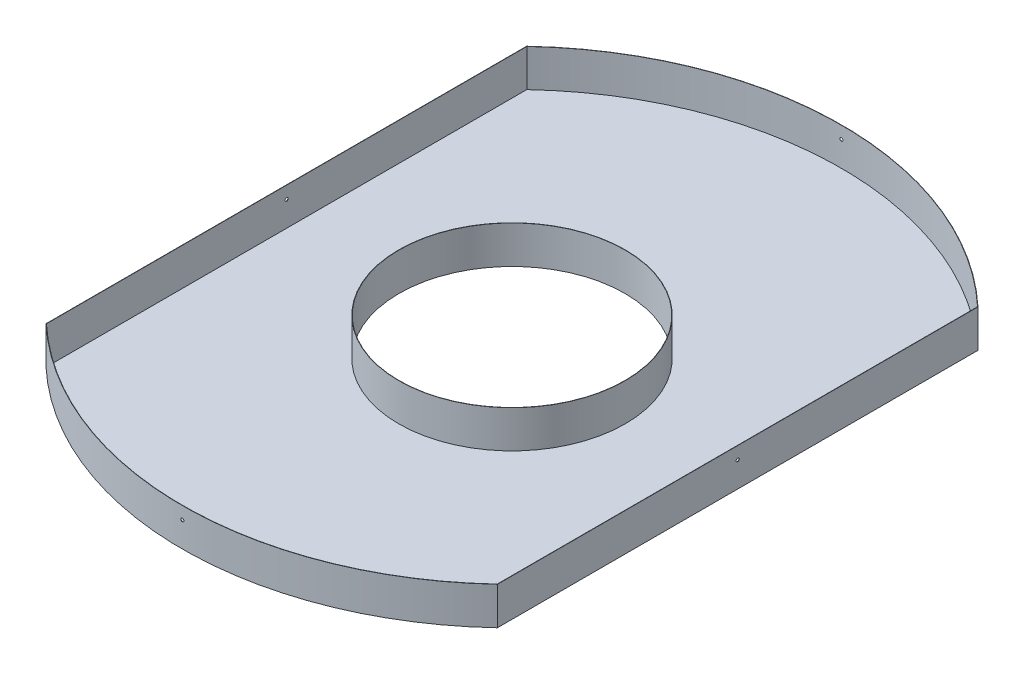
SolidWorks part; units mm, degrees
material "1345 Alloy"
ref_plane "Front Plane" through (0, 0, 0) normal (0, 0, 1) x (1, 0, 0)
ref_plane "Top Plane" through (0, 0, 0) normal (0, 1, 0) x (1, 0, 0)
ref_plane "Right Plane" through (0, 0, 0) normal (1, 0, 0) x (0, 0, -1)
sketch "Sketch1" plane through (0, 0, 0) normal (0, 1, 0) x (1, 0, 0)
  circle A0 centre (0, 0) radius 1750
extrude "Boss-Extrude1" add sketch "Sketch1" along normal blind 500
sketch "Sketch2" plane through (0, 500, 0) normal (0, 1, 0) x (1, 0, 0)
  circle A0 centre (0, 0) radius 900
extrude "Cut-Extrude2" cut sketch "Sketch2" against normal blind 300
sketch "Sketch10" plane through (0, 500, 0) normal (0, 1, 0) x (1, 0, 0)
  line L1 (-2200.588, -2811.5432) -> (2200.588, -2811.5432)
  line L2 (-2200.588, -2811.5432) -> (-2200.588, 2811.5432)
  line L3 (-2200.588, 2811.5432) -> (2200.588, 2811.5432)
  line L4 (2200.588, -2811.5432) -> (2200.588, 2811.5432)
  line L5 (-2200.588, -2811.5432) -> (2200.588, 2811.5432) construction
  line L6 (-2200.588, 2811.5432) -> (2200.588, -2811.5432) construction
  line L7 (-1198.0599, -2169.9586) -> (1198.0599, -2169.9586)
  line L8 (-1198.0599, -2169.9586) -> (-1198.0599, 2169.9586)
  line L9 (-1198.0599, 2169.9586) -> (1198.0599, 2169.9586)
  line L10 (1198.0599, -2169.9586) -> (1198.0599, 2169.9586)
  line L11 (-1198.0599, -2169.9586) -> (1198.0599, 2169.9586) construction
  line L12 (-1198.0599, 2169.9586) -> (1198.0599, -2169.9586) construction
  point P0 (0, 0)
  point P6 (0, 0)
extrude "Cut-Extrude10" cut sketch "Sketch10" against normal through all both and the other way through all
sketch "Sketch3" plane through (0, 0, 0) normal (0, -1, 0) x (1, 0, 0)
  circle A0 centre (0, 0) radius 600
extrude "Cut-Extrude3" cut sketch "Sketch3" against normal blind 300
shell "Shell1" thickness 1.5 removed face at (0, 500, 900)
sketch "Sketch11" plane through (0, 200, 0) normal (0, 1, 0) x (1, 0, 0)
  line L1 (-1546.6788, 2430.4952) -> (1546.6788, 2430.4952)
  line L2 (-1546.6788, 2430.4952) -> (-1546.6788, -2430.4952)
  line L3 (-1546.6788, -2430.4952) -> (1546.6788, -2430.4952)
  line L4 (1546.6788, 2430.4952) -> (1546.6788, -2430.4952)
  line L5 (-1546.6788, 2430.4952) -> (1546.6788, -2430.4952) construction
  line L6 (-1546.6788, -2430.4952) -> (1546.6788, 2430.4952) construction
  point P0 (0, 0)
extrude "Cut-Extrude11" cut sketch "Sketch11" along normal through all
ref_plane "Plane1" through (0, 0, 2000) normal (0, 0, 1) x (1, 0, 0)
sketch "Sketch7" plane through (0, 0, 2000) normal (0, 0, 1) x (1, 0, 0)
  circle A0 centre (0, 133.8976) radius 8.382
extrude "Cut-Extrude6" cut sketch "Sketch7" against normal blind 900
pattern_circular "CirPattern1" count 4 over 360 about axis through (0, 500, 0) along (0, -1, 0) of "Cut-Extrude6" reverse direction yes
ref_plane "Plane2" through (-1237.4369, 0, 1237.4369) normal (-0.7071, 0, 0.7071) x (0, -1, 0)
sketch "Sketch12" plane through (-1198.0599, 0, 0) normal (-1, 0, 0) x (0, 0, 1)
  line L0 (-828.0253, 88.1097) -> (-805.4725, 65.5569)
  line L1 (-805.4725, 65.5569) -> (-773.578, 65.5569)
  line L2 (-773.578, 65.5569) -> (-751.0253, 88.1097)
  line L3 (-751.0253, 88.1097) -> (-751.0253, 120.0042)
  line L4 (-751.0253, 120.0042) -> (-773.578, 142.5569)
  line L5 (-773.578, 142.5569) -> (-805.4725, 142.5569)
  line L6 (-805.4725, 142.5569) -> (-828.0253, 120.0042)
  line L7 (-828.0253, 120.0042) -> (-828.0253, 88.1097)
  circle A0 centre (-789.5253, 104.0569) radius 38.5 construction
  point P10 (0, 0)
  point P11 (0, 0)
extrude "Cut-Extrude13" [suppressed] cut sketch "Sketch12" against normal blind 10
sketch "Sketch13" plane through (0, 200, 0) normal (0, 1, 0) x (1, 0, 0)
  circle A0 centre (0, 0) radius 901.5 construction
  circle A1 centre (0, 0) radius 901.5
  circle A2 centre (0, 0) radius 601.5
extrude "Cut-Extrude14" cut sketch "Sketch13" against normal blind 10
